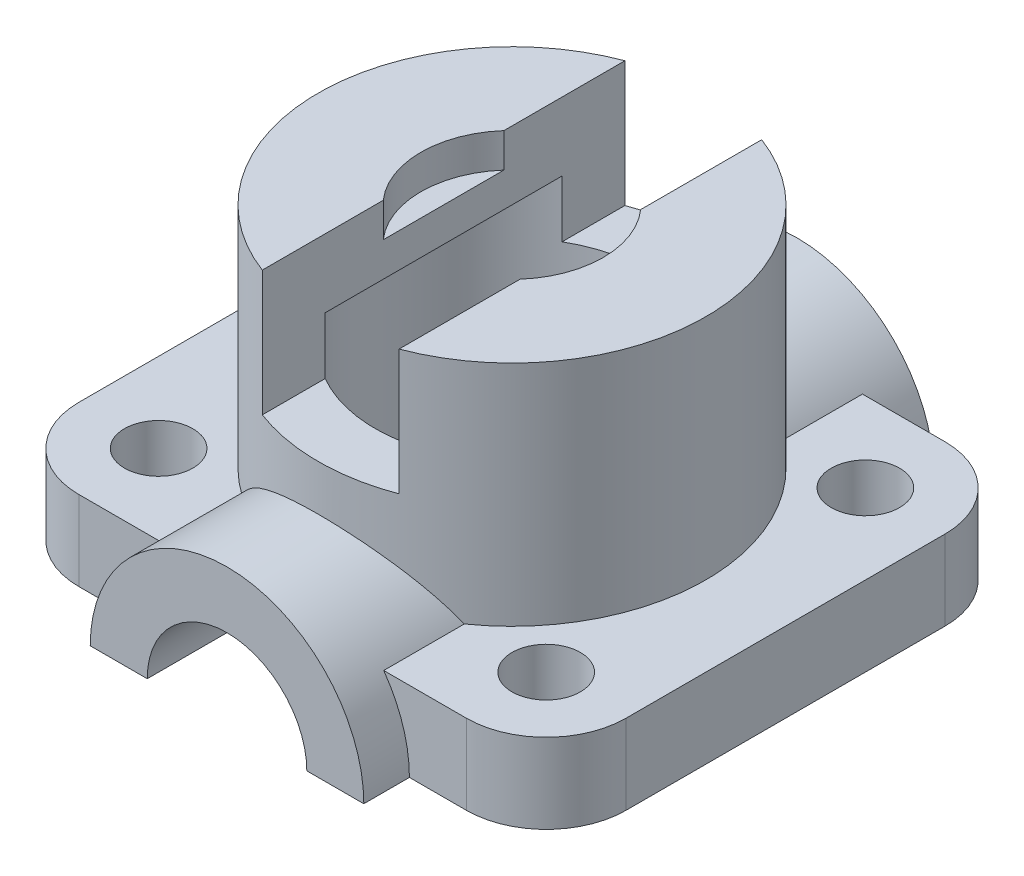
SolidWorks part; units mm, degrees
ref_plane "前视基准面" through (0, 0, 0) normal (0, 0, 1) x (1, 0, 0)
ref_plane "上视基准面" through (0, 0, 0) normal (0, 1, 0) x (1, 0, 0)
ref_plane "右视基准面" through (0, 0, 0) normal (1, 0, 0) x (0, 0, -1)
ref_plane "基准面4" through (0, 0, 25) normal (0, 0, 1) x (1, 0, 0)
sketch "草图1" plane through (0, 0, 25) normal (0, 0, 1) x (1, 0, 0)
  line L0 (0, 0) -> (41.2987, 0) construction
  line L1 (-12, 0) -> (-7, 0)
  line L2 (7, 0) -> (12, 0)
  arc A0 (12, 0) -> (-12, 0) centre (0, 0) ccw
  arc A1 (7, 0) -> (-7, 0) centre (0, 0) ccw
  dimension "D1" = 24
  dimension "D2" = 14
sketch "草图5" plane through (0, 0, 25) normal (0, 0, 1) x (1, 0, 0)
extrude "凸台-拉伸1" add sketch "草图1" against normal blind 50
sketch "草图7" plane through (0, 0, 0) normal (0, 1, 0) x (1, 0, 0)
  line L1 (-17, -21) -> (17, -21)
  line L2 (-24, -14) -> (-24, 14)
  line L3 (-17, 21) -> (17, 21)
  line L4 (24, -14) -> (24, 14)
  line L5 (-24, -21) -> (24, 21) construction
  line L6 (-24, 21) -> (24, -21) construction
  arc A0 (-24, 14) -> (-17, 21) centre (-17, 14) cw
  arc A1 (17, 21) -> (24, 14) centre (17, 14) cw
  arc A2 (-24, -14) -> (-17, -21) centre (-17, -14) ccw
  arc A3 (17, -21) -> (24, -14) centre (17, -14) ccw
  circle A4 centre (-17, 14) radius 3
  circle A5 centre (17, 14) radius 3
  circle A6 centre (17, -14) radius 3
  circle A7 centre (-17, -14) radius 3
  point P0 (0, 0)
  dimension "D3" = 7
  dimension "D4" = 7
  dimension "7" = 7
  dimension "D5" = 6
  dimension "D1" = 42
  dimension "D2" = 48
extrude "凸台-拉伸2" add sketch "草图7" along normal blind 7
sketch "草图8" plane through (0, 0, 0) normal (0, 1, 0) x (1, 0, 0)
  circle A0 centre (0, 0) radius 17
  dimension "D1" = 34
extrude "凸台-拉伸3" add sketch "草图8" along normal blind 27
ref_plane "基准面5" through (0, 27, 0) normal (0, 1, 0) x (1, 0, 0)
sketch "草图9" plane through (0, 27, 0) normal (0, 1, 0) x (1, 0, 0)
  circle A0 centre (0, 0) radius 8
  dimension "D1" = 16
extrude "切除-拉伸1" cut sketch "草图9" against normal blind 3
sketch "草图11" plane through (0, 0, 0) normal (0, 0, 1) x (1, 0, 0)
  line L0 (26.4, 27) -> (-26.4, 27) construction
  line L2 (-6, 27) -> (-6, 16)
  line L3 (-6, 16) -> (6, 16)
  line L4 (6, 27) -> (6, 16)
  line L5 (-6, 27) -> (6, 27)
  line L7 (0, 0) -> (0, 31.6175) construction
  point P0 (0, 27)
  dimension "D1" = 12
  dimension "D2" = 11
  dimension "D3" = 27
extrude "切除-拉伸3" cut sketch "草图11" against normal mid plane 40
sketch "草图12" plane through (0, 0, 0) normal (0, 1, 0) x (1, 0, 0)
  circle A0 centre (0, 0) radius 12
  dimension "D1" = 24
extrude "切除-拉伸4" cut sketch "草图12" along normal blind 21
sketch "草图13" plane through (0, 0, 25) normal (0, 0, 1) x (1, 0, 0)
  circle A0 centre (0, 0) radius 7
  dimension "D1" = 14
extrude "切除-拉伸5" cut sketch "草图13" against normal through all
